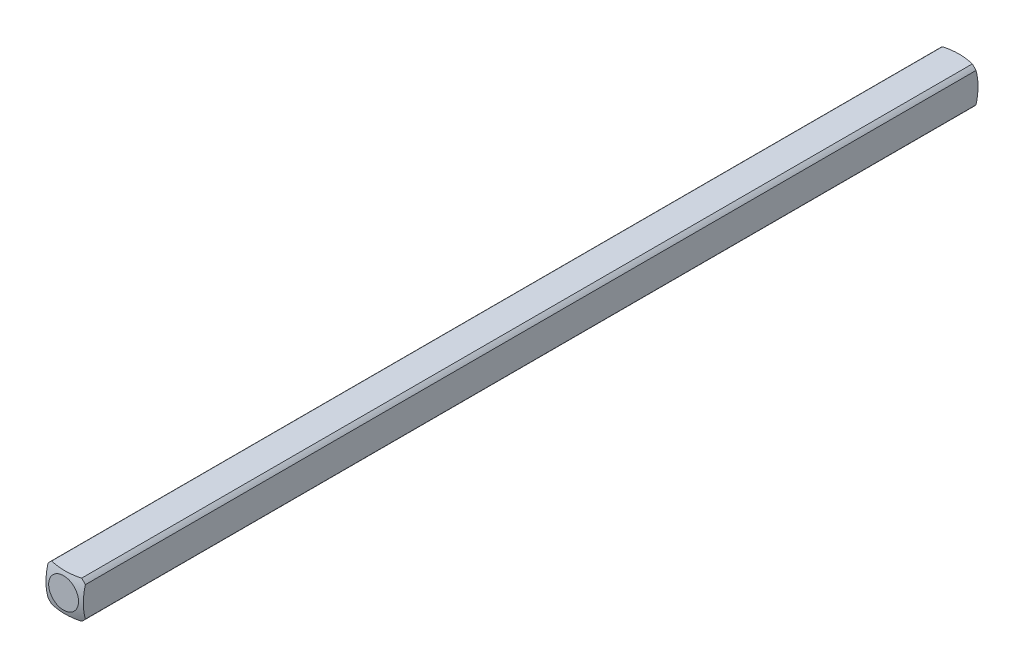
SolidWorks part; units mm, degrees
material "Custom Plastic"
ref_plane "Front Plane" through (0, 0, 0) normal (0, 0, 1) x (1, 0, 0)
ref_plane "Top Plane" through (0, 0, 0) normal (0, 1, 0) x (1, 0, 0)
ref_plane "Right Plane" through (0, 0, 0) normal (1, 0, 0) x (0, 0, -1)
sketch "Sketch1" plane through (0, 0, 0) normal (0, 0, 1) x (1, 0, 0)
  line L0 (-1.5875, -1.5875) -> (1.5875, 1.5875) construction
  line L1 (-1.5875, -1.5875) -> (1.5875, -1.5875)
  line L2 (-1.5875, -1.5875) -> (-1.5875, 1.5875)
  line L3 (-1.5875, 1.5875) -> (1.5875, 1.5875)
  line L4 (1.5875, -1.5875) -> (1.5875, 1.5875)
  dimension "D1" = 3.175
extrude "Boss-Extrude1" add sketch "Sketch1" along normal blind 38.1
sketch "Sketch2" plane through (0, 0, 0) normal (0, 0, -1) x (-1, 0, 0)
  circle A0 centre (0, 0) radius 2.032
  dimension "D1" = 4.064
extrude "Cut-Extrude1" cut sketch "Sketch2" against normal through all flip side to cut
ref_axis "Axis1" through (0, 0, 38.1) along (0, 0, -1)
sketch "Sketch3" plane through (0, 0, 0) normal (0, 1, 0) x (1, 0, 0)
  line L1 (-5.0537, -4.4027) -> (-5.0537, 5.7405)
  line L2 (-5.0537, 5.7405) -> (0, 5.7405)
  line L5 (0, -38.1) -> (0, 0) construction
  line L8 (0, 0.1609) -> (0, 5.7405)
  arc A0 (-5.0537, -4.4027) -> (0, 0.1609) centre (0, -4.9191) cw
  dimension "D1" = 5.08
revolve "Cut-Revolve1" cut sketch "Sketch3" angle 360 about axis through (0, 0, 38.1) along (0, 0, -1)
mirror "Mirror1" about plane through (0, 0, 38.1) normal (0, 0, -1) of bodies 103
